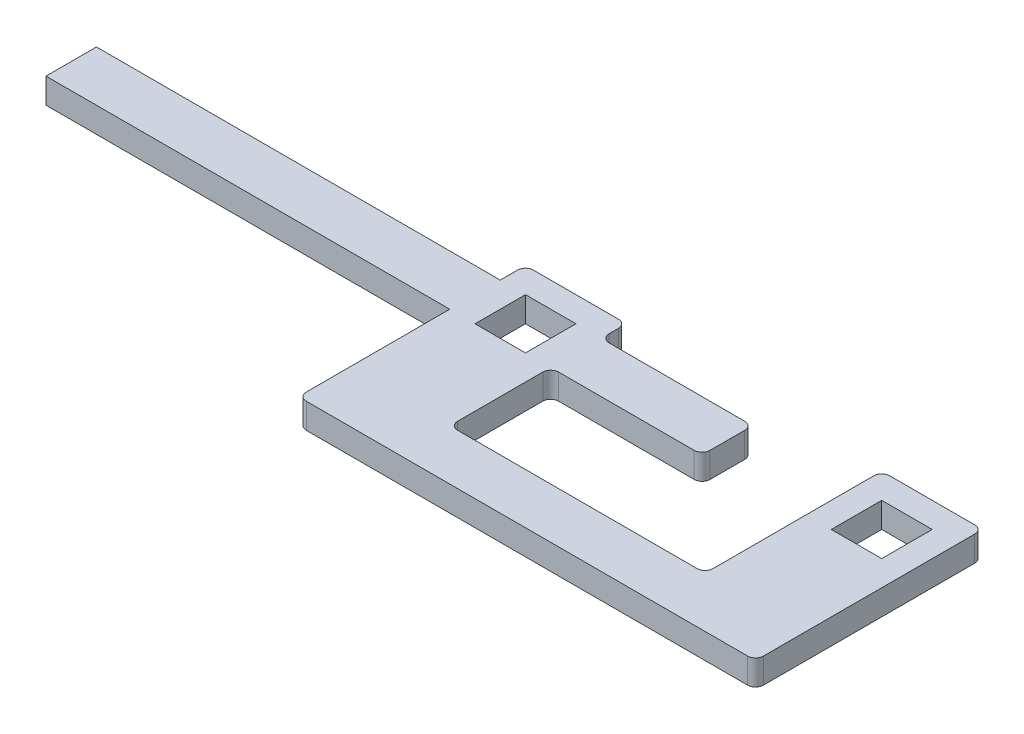
SolidWorks part; units mm, degrees
material "Beech"
ref_plane "Front Plane" through (0, 0, 0) normal (0, 0, 1) x (1, 0, 0)
ref_plane "Top Plane" through (0, 0, 0) normal (0, 1, 0) x (1, 0, 0)
ref_plane "Right Plane" through (0, 0, 0) normal (1, 0, 0) x (0, 0, -1)
sketch "Sketch1" plane through (0, 0, 0) normal (0, 1, 0) x (1, 0, 0)
  line L0 (0, 0) -> (0, 19.05)
  line L1 (0, 0) -> (19.05, 0)
  line L2 (0, 28.575) -> (12.7, 28.575)
  line L3 (12.7, 6.35) -> (12.7, 19.05)
  line L4 (44.825, 28.575) -> (44.825, 6.35)
  line L5 (44.825, 28.575) -> (57.525, 28.575)
  line L6 (42.65, 0) -> (57.525, 0)
  line L7 (57.525, 28.575) -> (57.525, 0)
  line L8 (12.7, 6.35) -> (44.825, 6.35)
  line L10 (12.7, 19.05) -> (31.75, 19.05)
  line L11 (19.05, 0) -> (42.65, 0)
  line L12 (3.175, 25.4) -> (3.175, 19.05)
  line L13 (3.175, 25.4) -> (9.525, 25.4)
  line L14 (3.175, 19.05) -> (9.525, 19.05)
  line L15 (9.525, 25.4) -> (9.525, 19.05)
  line L16 (48, 25.4) -> (48, 19.05)
  line L17 (48, 25.4) -> (54.35, 25.4)
  line L18 (48, 19.05) -> (54.35, 19.05)
  line L19 (54.35, 25.4) -> (54.35, 19.05)
  line L20 (0, 25.4) -> (-50.8, 25.4)
  line L21 (12.7, 25.4) -> (31.75, 25.4)
  line L22 (-50.8, 25.4) -> (-50.8, 19.05)
  line L23 (0, 19.05) -> (-50.8, 19.05)
  line L24 (0, 25.4) -> (0, 28.575)
  line L25 (31.75, 19.05) -> (31.75, 25.4)
  line L26 (12.7, 25.4) -> (12.7, 28.575)
  dimension "D1" = 6.35
  dimension "D2" = 6.35
  dimension "D3" = 6.35
  dimension "D4" = 6.35
  dimension "D5" = 44.825
  dimension "D6" = 3.175
  dimension "D7" = 19.05
  dimension "D8" = 3.175
  dimension "D9" = 3.175
  dimension "D10" = 3.175
  dimension "D11" = 3.175
  dimension "D12" = 3.175
  dimension "D13" = 19.05
  dimension "D14" = 50.8
  dimension "D15" = 6.35
  dimension "D16" = 6.35
  dimension "D17" = 19.05
extrude "Elastic_Extrude" add sketch "Sketch1" along normal blind 3.175
fillet "Elastic_CornerFillet" radius 1 12 edges at (12.7, 1.5875, -6.35) (44.825, 1.5875, -6.35) (44.825, 1.5875, -28.575) (57.525, 1.5875, -28.575) (57.525, 1.5875, 0) (0, 1.5875, 0) (0, 1.5875, -28.575) (12.7, 1.5875, -19.05) (31.75, 1.5875, -19.05) (31.75, 1.5875, -25.4) (12.7, 1.5875, -25.4) (12.7, 1.5875, -28.575)
equation "\"CageLeftBottomEdge\"=22.11mm"
equation "\"CageLeftTopEdge\"=22.11mm"
equation "\"CageRightBottomEdge\"=21.63mm"
equation "\"CageRightTopEdge\"=21.63mm"
equation "\"CageHeight\"=86.04mm"
equation "\"CageLength\"=73.76mm"
equation "\"CageTopScrewClearance\"=10mm"
equation "\"CageBottomScrewClearance\"=25mm"
equation "\"CageLeftTopDepth\"= 11.65mm"
equation "\"CageLeftBottomDepth\"=11.11mm"
equation "\"CageLeftTopHeight\"=8.56175mm"
equation "\"CageLeftBottomHeight\"=16mm"
equation "\"CageRightTopDepth\"= 11.05mm"
equation "\"CageRightBottomDepth\"=10.58mm"
equation "\"CageRightTopHeight\"=9.6mm"
equation "\"CageRightBottomHeight\"=15.49mm"
equation "\"CageLeftTopChannelDepth\"=2.41908mm"
equation "\"CageLeftBottomChannelDepth\"=2.588mm"
equation "\"CageLeftChannelHeight\"=11.7mm"
equation "\"CageRightTopChannelDepth\"=2.32mm"
equation "\"CageRightBottomChannelDepth\"=2.318mm"
equation "\"CageRightChannelHeight\"=10mm"
equation "\"CageChanRelHeight\"=23.99mm"
equation "\"CageChanRelDepth\"=5.492mm"
equation "\"CageChamberRadius\"=16.261mm"
equation "\"CageScrewDiameter\"=4.8mm"
equation "\"CageSetScrewDiameter\"=3.5mm"
equation "\"CageAxleRadius\"=6.639mm"
equation "\"CageAxleKeyHeight\"=1.619mm"
equation "\"CageAxleKeyWidth\"=2.662mm"
equation "\"CageHoseWindowWidth\"=16.29mm"
equation "\"CageHoseWindowHeight\"=26.5mm"
equation "\"CageHoseWindow-Edge\"=8.89mm"
equation "\"CageScrew-VerticalEdge\"=5.0mm"
equation "\"CageScrew-HorizontalEdge\"=7.5mm"
equation "\"CageScrew-HoseCornerScrewEdge\"=4.45mm"
equation "\"CageAxle-BottomEdge\"=56.05mm"
equation "\"CageAxle-FrontEdge\"=46.03mm"
equation "\"CageBackSetScrew-Axle\"=40mm"
equation "\"CageFrontSetScrew-Axle\"=22mm"
equation "\"CageVelocityWindow-BackEdge\"=34.8mm"
equation "\"CageVelocityWindow-BottomEdge\"=27.55mm"
equation "\"CageVelocityWindowHeight\"=22.29mm"
equation "\"CageVelocityWindowWidth\"=12.61mm"
equation "\"TriggerSlot-BottomEdge\"=6.35mm"
equation "\"TriggerSlot-FrontEdge\"=15mm"
equation "\"TriggerSlotSize\"=6.7mm"
equation "\"TriggerRackOffset\"=.236224in"
equation "\"TriggerSlotSizeInt\"=.25in"
equation "\"MotorMountLegLength\"=.25in"
equation "\"GearOffset\"=.264907in"
equation "\"TriggerSlotSpacing\"=.25in"
equation "\"TriggerMiniSlotWidth\"=3.5mm"
equation "\"TriggerRackWidth\"=6.5mm"
equation "\"TGMGearFaceDiameter\"=24.40mm"
equation "\"TGMCylinderLength\"=15.00mm"
equation "\"TGMScrewHole-Center\"=8.70mm"
equation "\"TGMScrewHoleDiameter\"=5.04mm"
equation "\"TGMCenterHoleDiameter\"=9.50mm"
equation "\"TGMShaftCollarSideLength\"=19.00mm"
equation "\"TGMShaftCollarDockingDepth\"=7.00mm"
equation "\"whitemotordepth\"=11.27mm"
equation "\"whitemotorbackdepth\"=3.845mm"
equation "\"whitemotoraxledepth\" = 3.5mm"
equation "\"whitemotoraxleoffset\"=11.4mm"
equation "\"whitemotorwidth\"=12.07mm"
equation "\"whitemotorheight\"=16.68mm"
equation "\"whitemotorcylinderlength\" =13.04mm"
equation "\"whitemotorcylinderradius\"=3.845mm"
equation "\"whitemotorcylinderoffset\"=2.35mm"
equation "\"whitemotorcutoutlength\"=1.88mm"
equation "\"whitemotorouterrad\"=5mm"
equation "\"D4@Sketch1\"=\"elasticrackpegsize\""
equation "\"elasticrackpegspacing\"=1.76476378in"
equation "\"D5@Sketch1\"=\"elasticrackpegspacing\""
equation "\"D6@Sketch1\"=\"elasticrackpegbuffer\""
equation "\"elasticrackpegsize\"=.25in"
equation "\"D1@Sketch1\"=\"elasticrackpegsize\""
equation "\"D2@Sketch1\"=\"elasticrackpegsize\""
equation "\"D3@Sketch1\"=\"elasticrackpegsize\""
equation "\"elasticracklength\"=2in"
equation "\"D14@Sketch1\"=\"elasticracklength\""
equation "\"elasticrackpegbuffer\"=.125in"
equation "\"D11@Sketch1\"=\"elasticrackpegbuffer\""
equation "\"D12@Sketch1\"=\"elasticrackpegbuffer\""
equation "\"D10@Sketch1\"=\"elasticrackpegbuffer\""
equation "\"D9@Sketch1\"=\"elasticrackpegbuffer\""
equation "\"D8@Sketch1\"=\"elasticrackpegbuffer\""
equation "\"elasticbaybuffer\"=.25in"
equation "\"D15@Sketch1\"=\"elasticbaybuffer\""
equation "\"D16@Sketch1\"=\"elasticbaybuffer\""
equation "\"whitemotorinnerrad\"=2.95mm"
equation "\"elasticbaydepth\"=.75in"
equation "\"D7@Sketch1\"=\"elasticbaydepth\""
equation "\"D13@Sketch1\"=\"elasticbaydepth\""
equation "\"D17@Sketch1\"=\"elasticbaydepth\""
equation "\"elasticdepth\"=.125in"
equation "\"D1@Elastic_Extrude\"=\"elasticdepth\""
equation "\"motormountwidth\"=12mm"
equation "\"motormountcornerfillet\"=3mm"
equation "\"pandiscradius\"=14in"
equation "\"towermaterialwidth\"=.25in"
equation "\"towerslotlength\"=.5in"
equation "\"towermarkerspace\"=5in"
equation "\"towerslothorizoffset\"=1in"
equation "\"towerslothorizspacing\"=2in"
equation "\"towerslotvertoffset\"=3in"
equation "\"towerslotvertspacing\"=2in"
equation "\"towerheight\"=12in"
equation "\"towerupslot\"=1in"
equation "\"toweraxle\"=.5in"
equation "\"towerplatslotoffset\"=1.5in"
equation "\"towermotorpanelheight\"=10in"
equation "\"towerplatdepth\"=2in"
equation "\"stepperouterrad\"=10mm"
equation "\"stepperscrewsize\"=3.45mm"
equation "\"stepperscrewc2c\"=49.5mm"
equation "\"stepperdepthoffset\"=24mm"
equation "\"stepperhorizoffset\"=22.91mm"
